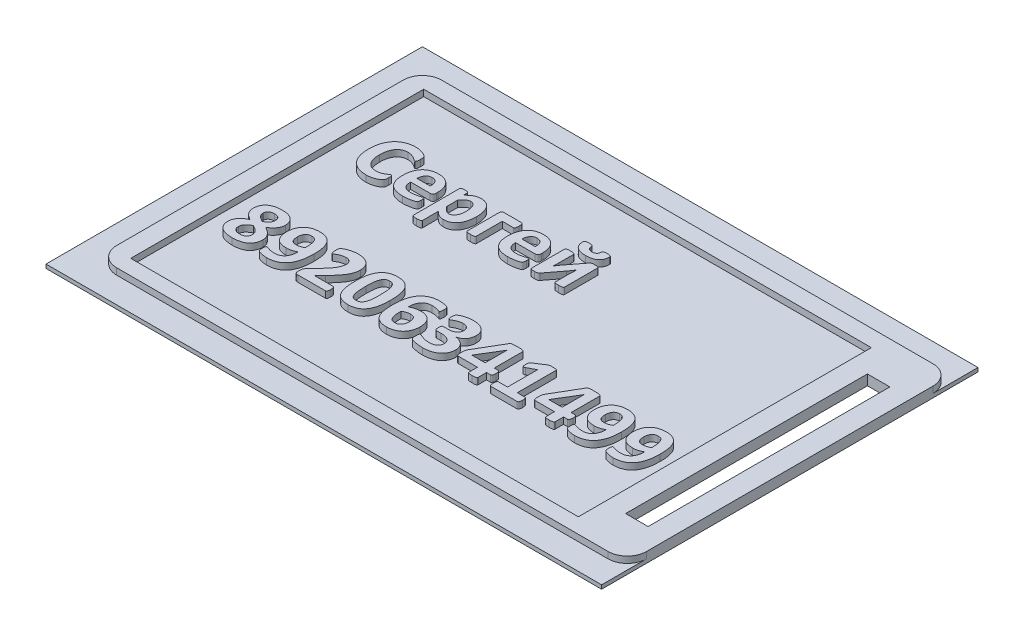
SolidWorks part; units mm, degrees
ref_plane "Спереди" through (0, 0, 0) normal (0, 0, 1) x (1, 0, 0)
ref_plane "Сверху" through (0, 0, 0) normal (0, 1, 0) x (1, 0, 0)
ref_plane "Справа" through (0, 0, 0) normal (1, 0, 0) x (0, 0, -1)
other "Configuration Table"
sketch "Эскиз1" plane through (0, 0, 0) normal (0, 1, 0) x (1, 0, 0)
  line L1 (-43.25, -29.3) -> (43.25, -29.3)
  line L2 (-43.25, -29.3) -> (-43.25, 29.3)
  line L3 (-43.25, 29.3) -> (43.25, 29.3)
  line L4 (43.25, -29.3) -> (43.25, 29.3)
  line L5 (0, 29.3) -> (0, -29.3) construction
  line L6 (-43.25, 0) -> (43.25, 0) construction
  point P0 (0, 0)
  dimension "D1" = 86.5
  dimension "D2" = 58.6
extrude "Бобышка-Вытянуть1" add sketch "Эскиз1" along normal blind 0.6
sketch "Эскиз2" plane through (0, 0.6, 0) normal (0, 1, 0) x (1, 0, 0)
  line L0 (43.25, -29.3) -> (43.25, 29.3) construction
  line L1 (43.25, 25.3) -> (-39.25, 25.3)
  line L2 (43.25, 25.3) -> (43.25, -25.3)
  line L3 (43.25, -25.3) -> (-39.25, -25.3)
  line L4 (-39.25, 25.3) -> (-39.25, -25.3)
  line L5 (2, -25.3) -> (2, 25.3) construction
  line L6 (43.25, 0) -> (-39.25, 0) construction
  line L7 (43.25, 29.3) -> (-43.25, 29.3) construction
  line L8 (-43.25, -29.3) -> (43.25, -29.3) construction
  line L9 (-43.25, 29.3) -> (-43.25, -29.3) construction
  point P968 (2, 0)
  dimension "D1" = 4
  dimension "D2" = 4
  dimension "D3" = 4
extrude "Бобышка-Вытянуть2" add sketch "Эскиз2" along normal blind 1
sketch "Эскиз3" plane through (0, 1.6, 0) normal (0, 1, 0) x (1, 0, 0)
  line L1 (40.0107, -18.8234) -> (36.5087, -18.8234)
  line L2 (40.0107, -18.8234) -> (40.0107, 18.8234)
  line L3 (40.0107, 18.8234) -> (36.5087, 18.8234)
  line L4 (36.5087, -18.8234) -> (36.5087, 18.8234)
  line L5 (38.2597, 18.8234) -> (38.2597, -18.8234) construction
  line L6 (40.0107, 0) -> (36.5087, 0) construction
  point P0 (38.2597, 0)
extrude "Вырез-Вытянуть1" cut sketch "Эскиз3" against normal blind 2
sketch "Эскиз4" plane through (0, 1.6, 0) normal (0, 1, 0) x (1, 0, 0)
  line L0 (-39.25, 0) -> (35.6332, 0) construction
  line L1 (-39.25, 25.3) -> (-39.25, -25.3) construction
  line L3 (-36.4211, 22.6756) -> (33.2693, 22.6756)
  line L4 (-36.4211, 22.6756) -> (-36.4211, -22.9383)
  line L5 (-36.4211, -22.9383) -> (33.2693, -22.9383)
  line L6 (33.2693, 22.6756) -> (33.2693, -22.9383)
  line L7 (-1.5759, -22.9383) -> (-1.5759, 22.6756) construction
  line L8 (-36.4211, -0.1313) -> (33.2693, -0.1313) construction
  point P313 (-1.5759, -0.1313)
extrude "Вырез-Вытянуть2" cut sketch "Эскиз4" against normal blind 1
fillet "Скругление1" radius 3 1 edges at (43.25, 1.1, -25.3)
fillet "Скругление2" radius 3 1 edges at (-39.25, 1.1, -25.3)
fillet "Скругление3" radius 3 1 edges at (-39.25, 1.1, 25.3)
fillet "Скругление4" radius 3 1 edges at (43.25, 1.1, 25.3)
sketch "Эскиз5" plane through (0, 0.6, 0) normal (0, 1, 0) x (1, 0, 0)
  text T0 "89206341499" font "Calibri" height in points 28
extrude "Бобышка-Вытянуть3" add sketch "Эскиз5" along normal blind 1
sketch "Эскиз6" plane through (0, 0.6, 0) normal (0, 1, 0) x (1, 0, 0)
  text T0 "Сергей" font "Calibri" height in points 28
extrude "Бобышка-Вытянуть4" add sketch "Эскиз6" along normal blind 1
